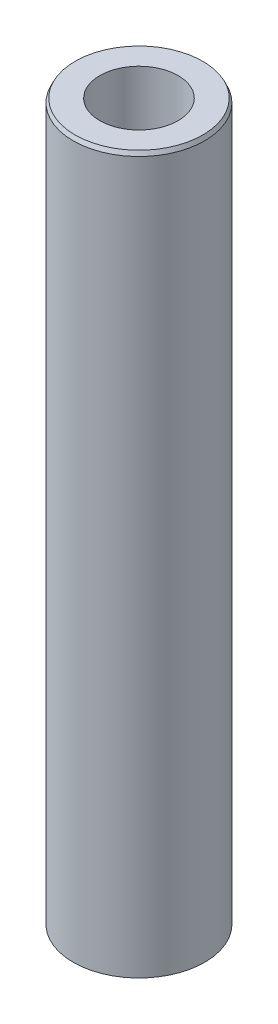
SolidWorks part; units mm, degrees
ref_plane "Front Plane" through (0, 0, 0) normal (0, 0, 1) x (1, 0, 0)
ref_plane "Top Plane" through (0, 0, 0) normal (0, 1, 0) x (1, 0, 0)
ref_plane "Right Plane" through (0, 0, 0) normal (1, 0, 0) x (0, 0, -1)
sketch "Sketch1" plane through (0, 0, 0) normal (0, 1, 0) x (1, 0, 0)
  circle A0 centre (0, 0) radius 55
  dimension "SHAFT_OD" = 110
extrude "Boss-Extrude1" add sketch "Sketch1" along normal blind 600
sketch "Sketch2" plane through (0, 0, 0) normal (0, 1, 0) x (1, 0, 0)
  circle A0 centre (0, 0) radius 32.7203
  dimension "BORE_D" = 65.4406
extrude "Cut-Extrude1" cut sketch "Sketch2" along normal through all
chamfer "Chamfer1" distance 3.4167 angle 25.179 2 edges at (0, 600, 55) (0, 0, 55) first distance on face at (0, 600, 55) first distance on face at (0, 0, 32.7203)
